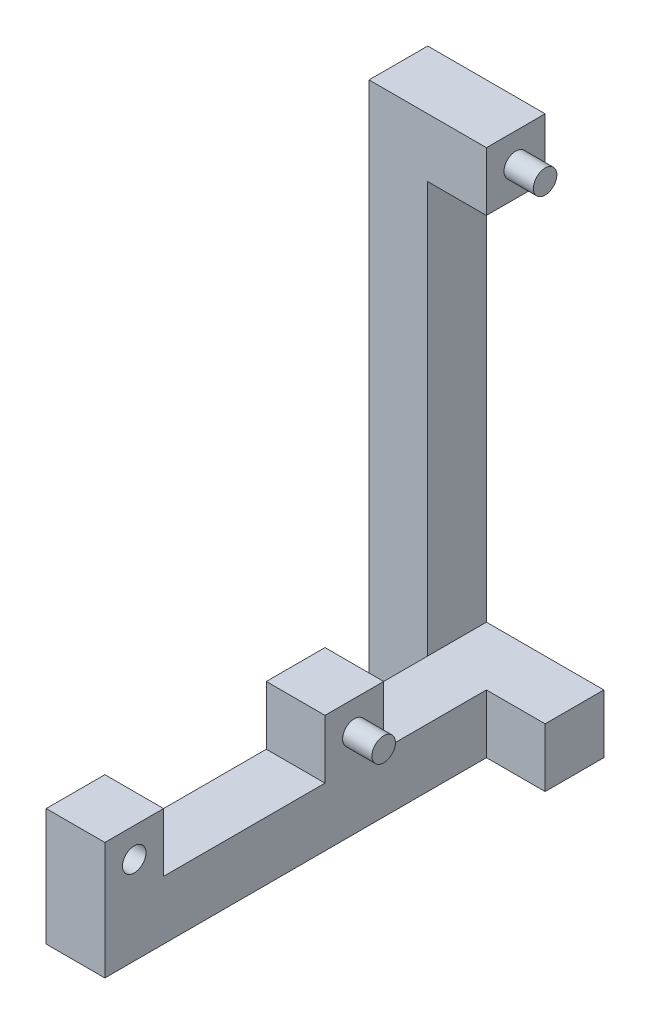
SolidWorks part; units mm, degrees
material "Hexcel AS4C (3000 Filaments)"
ref_plane "Front Plane" through (0, 0, 0) normal (0, 0, 1) x (1, 0, 0)
ref_plane "Top Plane" through (0, 0, 0) normal (0, 1, 0) x (1, 0, 0)
ref_plane "Right Plane" through (0, 0, 0) normal (1, 0, 0) x (0, 0, -1)
sketch "LowerBase" plane through (0, 0, 0) normal (1, 0, 0) x (0, 0, -1)
  line L9 (0, 0) -> (-1500, 0)
  line L10 (0, 0) -> (0, 200)
  line L11 (0, 200) -> (-1500, 200)
  line L12 (-1500, 0) -> (-1500, 200)
  line L13 (-1500, 200) -> (-1300, 200)
  line L14 (-1500, 200) -> (-1500, 400)
  line L15 (-1500, 400) -> (-1300, 400)
  line L16 (-1300, 200) -> (-1300, 400)
  line L17 (-750, 200) -> (-550, 200)
  line L18 (-750, 200) -> (-750, 400)
  line L19 (-750, 400) -> (-550, 400)
  line L20 (-550, 200) -> (-550, 400)
  dimension "D2" = 1500
  dimension "D1" = 200
  dimension "D3" = 200
  dimension "D4" = 200
  dimension "D5" = 200
  dimension "D6" = 200
  dimension "D7" = 550
  dimension "D8" = 550
extrude "Boss-Extrude1" add sketch "LowerBase" along normal blind 200 contours L12 L9 L10 L11 | L14 L15 L16 L13 | L19 L20 L17 L18
sketch "UpperBase" plane through (0, 0, 0) normal (1, 0, 0) x (0, 0, -1)
  line L1 (0, 0) -> (-200, 0)
  line L2 (0, 0) -> (0, 1800)
  line L3 (0, 1800) -> (-200, 1800)
  line L4 (-200, 0) -> (-200, 1800)
  dimension "D1" = 1800
  dimension "D2" = 200
extrude "Boss-Extrude2" add sketch "UpperBase" along direction (-1, 0, 0) on the side against the normal blind 200
sketch "TopPivot" plane through (0, 0, 0) normal (1, 0, 0) x (0, 0, -1)
  line L1 (-200, 1800) -> (0, 1800)
  line L2 (-200, 1800) -> (-200, 1600)
  line L3 (-200, 1600) -> (0, 1600)
  line L4 (0, 1800) -> (0, 1600)
  dimension "D1" = 200
  dimension "D2" = 200
extrude "Boss-Extrude3" add sketch "TopPivot" along normal blind 200
sketch "PressTable" plane through (0, 0, 0) normal (1, 0, 0) x (0, 0, -1)
  line L0 (0, 200) -> (-550, 200) construction
  line L1 (0, 0) -> (-200, 0)
  line L2 (0, 0) -> (0, 200)
  line L3 (0, 200) -> (-200, 200)
  line L4 (-200, 0) -> (-200, 200)
  dimension "D1" = 200
  dimension "D2" = 200
extrude "Boss-Extrude4" add sketch "PressTable" along normal blind 400
sketch "MiddleRivet" plane through (0, 0, 0) normal (1, 0, 0) x (0, 0, -1)
  line L0 (-750, 200) -> (-550, 400) construction
  circle A0 centre (-650, 300) radius 40
  dimension "D1" = 80
extrude "Boss-Extrude5" add sketch "MiddleRivet" along normal blind 300
sketch "TopRivet" plane through (0, 0, 0) normal (1, 0, 0) x (0, 0, -1)
  line L0 (0, 1800) -> (-200, 1600) construction
  circle A0 centre (-100, 1700) radius 40
  dimension "D1" = 80
extrude "Boss-Extrude6" add sketch "TopRivet" along normal blind 300
sketch "Sketch6" plane through (0, 0, 0) normal (1, 0, 0) x (0, 0, -1)
  line L0 (-1300, 400) -> (-1500, 200) construction
  line L1 (-1500, 0) -> (-1500, 400) construction
  circle A0 centre (-1400, 300) radius 40
  dimension "D1" = 80
extrude "Cut-Extrude1" cut sketch "Sketch6" against normal through all both and the other way through all
equation "\"baseFrameHeight\"= 180cm"
equation "\"baseFrameLength\" = 150cm"
equation "\"baseFrameThickness\"= 20cm"
equation "\"D2@LowerBase\" = \"baseFrameLength\""
equation "\"D1@LowerBase\" = \"baseFrameThickness\""
equation "\"D3@LowerBase\" = \"baseFrameThickness\""
equation "\"D4@LowerBase\" = \"baseFrameThickness\""
equation "\"D5@LowerBase\" = \"baseFrameThickness\""
equation "\"D6@LowerBase\" = \"baseFrameThickness\""
equation "\"D1@Boss-Extrude1\"=\"baseFrameThickness\""
equation "\"D1@UpperBase\" = \"baseFrameHeight\""
equation "\"D2@UpperBase\" = \"baseFrameThickness\""
equation "\"D1@Boss-Extrude2\"=\"baseFrameThickness\""
equation "\"D1@TopPivot\" = \"baseFrameThickness\""
equation "\"D2@TopPivot\" = \"baseFrameThickness\""
equation "\"D1@Boss-Extrude3\"=\"baseFrameThickness\""
equation "\"D2@PressTable\" = \"baseFrameThickness\""
equation "\"D1@Boss-Extrude4\"=2*\"baseFrameThickness\""
equation "\"D1@MiddleRivet\" = \"HoleMountDiameter@PrintingPress.Assembly\""
equation "\"D1@Boss-Extrude5\" = \"RivetLength@PrintingPress.Assembly\" + \"baseFrameThickness\""
equation "\"D1@TopRivet\" = \"HoleMountDiameter@PrintingPress.Assembly\""
equation "\"D1@Boss-Extrude6\" = \"RivetLength@PrintingPress.Assembly\" + \"baseFrameThickness\""
equation "\"D1@Sketch6\" = \"HoleMountDiameter@PrintingPress.Assembly\""
